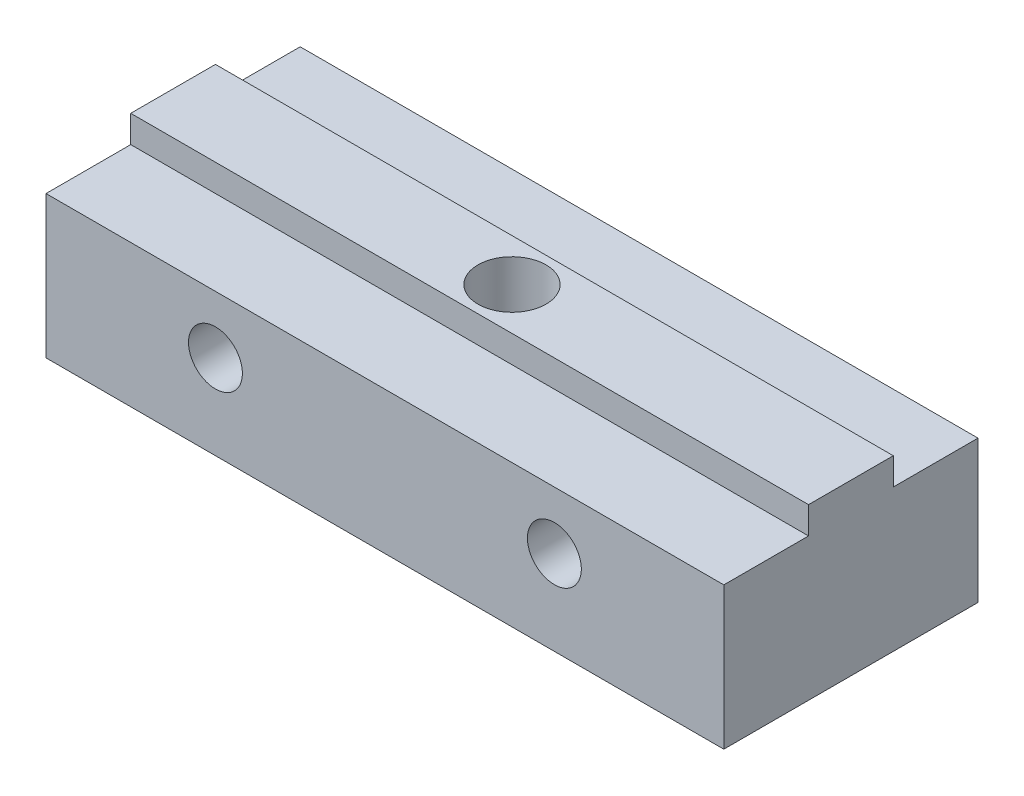
SolidWorks part; units mm, degrees
ref_plane "Front Plane" through (0, 0, 0) normal (0, 0, 1) x (1, 0, 0)
ref_plane "Top Plane" through (0, 0, 0) normal (0, 1, 0) x (1, 0, 0)
ref_plane "Right Plane" through (0, 0, 0) normal (1, 0, 0) x (0, 0, -1)
sketch "Sketch1" plane through (0, 0, 0) normal (0, 1, 0) x (1, 0, 0)
  line L1 (25.4, -9.525) -> (-25.4, -9.525)
  line L2 (25.4, -9.525) -> (25.4, 9.525)
  line L3 (25.4, 9.525) -> (-25.4, 9.525)
  line L4 (-25.4, -9.525) -> (-25.4, 9.525)
  line L5 (25.4, -9.525) -> (-25.4, 9.525) construction
  line L6 (25.4, 9.525) -> (-25.4, -9.525) construction
  point P0 (0, 0)
  dimension "D1" = 50.8
  dimension "D2" = 19.05
extrude "Boss-Extrude1" add sketch "Sketch1" along normal blind 12.7
sketch "Sketch2" plane through (0, 12.7, 0) normal (0, 1, 0) x (1, 0, 0)
  line L0 (-25.4, 9.525) -> (-25.4, -9.525) construction
  line L1 (25.4, -3.175) -> (-25.4, -3.175)
  line L2 (25.4, -3.175) -> (25.4, 3.175)
  line L3 (25.4, 3.175) -> (-25.4, 3.175)
  line L4 (-25.4, -3.175) -> (-25.4, 3.175)
  line L5 (25.4, -3.175) -> (-25.4, 3.175) construction
  line L6 (25.4, 3.175) -> (-25.4, -3.175) construction
  point P0 (0, 0)
  dimension "D1" = 6.35
hole_wizard "#10-32 Tapped Hole1" positions "Sketch3" profile "Sketch4" tap size "#10-32" standard "ANSI Inch" end condition through all
sketch "Sketch3" plane through (0, 0, -9.525) normal (0, 0, -1) x (-1, 0, 0)
  line L0 (-25.4, 6.35) -> (25.4, 6.35) construction
  line L1 (-25.4, 12.7) -> (-25.4, 0) construction
  line L2 (25.4, 12.7) -> (25.4, 0) construction
  point P9 (-12.7, 6.35)
  point P11 (12.7, 6.35)
  dimension "D1" = 12.7
  dimension "D2" = 12.7
sketch "Sketch4" plane through (-12.7, 6.35, -9.525) normal (1, 0, 0) x (0, 1, 0)
  line L0 (0, 0) -> (0, 19.05)
  line L1 (0, 19.05) -> (2.0193, 19.05)
  line L2 (2.0193, 19.05) -> (2.0193, 0)
  line L5 (2.0193, 0) -> (0, 0)
  line L11 (0, -6.35) -> (0, 107.95) construction
  dimension "Thread Major Dia." = 4.0386
  dimension "Thru Tap Drill Depth" = 19.05
hole_wizard "CBORE for #10 Binding Head Machine Screw1" positions "Sketch5" profile "Sketch6" counterbore size "#10" standard "ANSI Inch" end condition through all
sketch "Sketch5" plane through (0, 0, 0) normal (0, -1, 0) x (-1, 0, 0)
  point P24 (0, 0)
sketch "Sketch6" plane through (0, 0, 0) normal (1, 0, 0) x (0, 0, -1)
  line L0 (0, 0) -> (0, 12.7)
  line L1 (0, 12.7) -> (2.5527, 12.7)
  line L3 (2.5527, 12.7) -> (2.5527, 2.54)
  line L4 (2.5527, 2.54) -> (5.5562, 2.54)
  line L5 (5.5562, 2.54) -> (5.5562, 0)
  line L7 (5.5562, 0) -> (0, 0)
  line L11 (0, -6.35) -> (0, 107.95) construction
  dimension "Thru Hole Dia." = 5.1054
  dimension "Thru Hole Depth" = 12.7
  dimension "C'Bore Dia." = 11.1125
  dimension "C'Bore Depth" = 2.54
extrude "Cut-Extrude1" cut sketch "Sketch2" against normal blind 2.032 flip side to cut contours L3 L4 L1 L2
